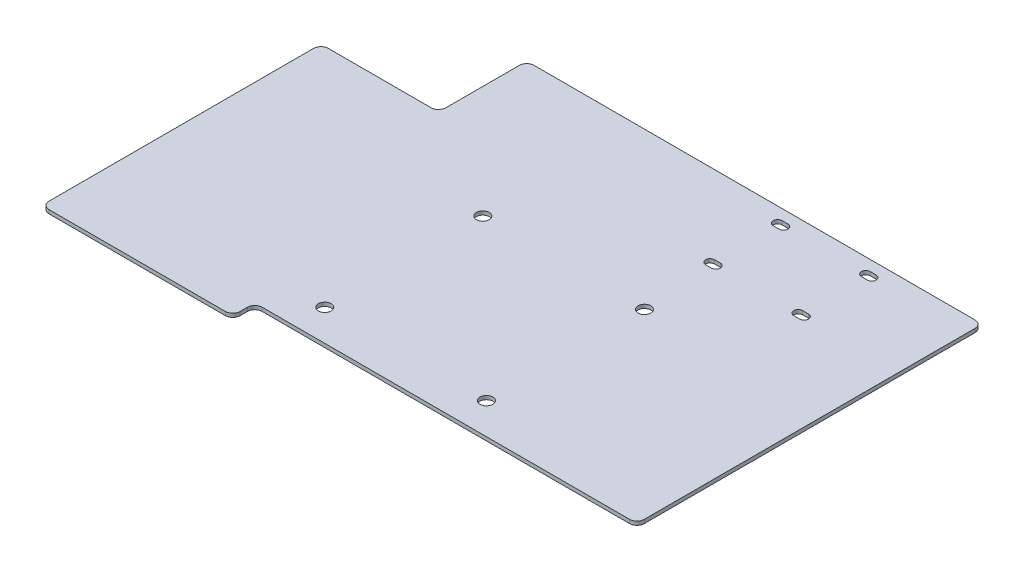
SolidWorks part; units mm, degrees
ref_plane "Front Plane" through (0, 0, 0) normal (0, 0, 1) x (1, 0, 0)
ref_plane "Top Plane" through (0, 0, 0) normal (0, 1, 0) x (1, 0, 0)
ref_plane "Right Plane" through (0, 0, 0) normal (1, 0, 0) x (0, 0, -1)
sketch "Sketch1" plane through (0, 0, 0) normal (0, 1, 0) x (1, 0, 0)
  line L1 (0, 0) -> (247.65, 0)
  line L2 (0, 0) -> (0, 120.65)
  line L3 (50.8, 158.75) -> (247.65, 158.75)
  line L4 (247.65, 0) -> (247.65, 158.75)
  line L15 (0, 120.65) -> (50.8, 120.65)
  line L16 (50.8, 158.75) -> (50.8, 120.65)
  line L21 (351.9786, 184.7613) -> (351.9786, -3.4747) construction
  point P1 (-19.9866, 3.5414)
  point P2 (0, 0)
  dimension "D1" = 158.75
  dimension "D2" = 351.9786
  dimension "D4" = 247.65
  dimension "D6" = 38.1
  dimension "D7" = 50.8
extrude "Boss-Extrude1" add sketch "Sketch1" along normal blind 1.6002 contours L1 L4 L3 L2 L15 L16 region at (128.9214, 0, -76.2514)
sketch "Sketch3" plane through (0, 1.6002, 0) normal (0, 1, 0) x (1, 0, 0)
  line L0 (82.55, 0) -> (82.55, 9.525)
  line L1 (0, 0) -> (247.65, 0) construction
  line L2 (82.55, 9.525) -> (247.65, 9.525)
  line L8 (247.65, 0) -> (247.65, 158.75) construction
  line L10 (247.65, 0) -> (82.55, 0)
  line L11 (0, 0) -> (0, 120.65) construction
  line L12 (247.65, 9.525) -> (247.65, 0)
  point P5 (247.65, 9.525)
  point P7 (247.65, 12.1552)
  dimension "D1" = 82.55
  dimension "D2" = 9.525
extrude "Cut-Extrude1" cut sketch "Sketch3" against normal through all
fillet "Fillet1" radius 3.175 8 edges at (82.55, 0.8001, 0) (0, 0.8001, -120.65) (50.8, 0.8001, -120.65) (50.8, 0.8001, -158.75) (247.65, 0.8001, -158.75) (247.65, 0.8001, -9.525) (82.55, 0.8001, -9.525) (0, 0.8001, 0)
sketch "Sketch4" plane through (0, 1.6002, 0) normal (0, 1, 0) x (1, 0, 0)
  line L0 (165.653, 152.32) -> (168.193, 152.32) construction
  line L1 (165.653, 154.225) -> (168.193, 154.225)
  line L2 (165.653, 150.415) -> (168.193, 150.415)
  line L5 (203.753, 152.32) -> (206.293, 152.32) construction
  line L6 (203.753, 154.225) -> (206.293, 154.225)
  line L7 (203.753, 150.415) -> (206.293, 150.415)
  line L8 (203.753, 123.11) -> (206.293, 123.11) construction
  line L9 (203.753, 125.015) -> (206.293, 125.015)
  line L10 (203.753, 121.205) -> (206.293, 121.205)
  line L11 (165.653, 123.11) -> (168.193, 123.11) construction
  line L12 (165.653, 125.015) -> (168.193, 125.015)
  line L13 (165.653, 121.205) -> (168.193, 121.205)
  line L15 (205.023, 123.11) -> (166.923, 123.11) construction
  line L16 (205.023, 123.11) -> (205.023, 152.32) construction
  line L17 (205.023, 152.32) -> (166.923, 152.32) construction
  line L18 (166.923, 123.11) -> (166.923, 152.32) construction
  line L19 (205.023, 123.11) -> (166.923, 152.32) construction
  line L20 (205.023, 152.32) -> (166.923, 123.11) construction
  line L21 (222.488, 125.015) -> (149.458, 125.015) construction
  line L22 (222.488, 125.015) -> (222.488, 150.415) construction
  line L23 (222.488, 150.415) -> (149.458, 150.415) construction
  line L24 (149.458, 125.015) -> (149.458, 150.415) construction
  line L25 (222.488, 125.015) -> (149.458, 150.415) construction
  line L26 (222.488, 150.415) -> (149.458, 125.015) construction
  arc A0 (165.653, 154.225) -> (165.653, 150.415) centre (165.653, 152.32) ccw
  arc A1 (168.193, 150.415) -> (168.193, 154.225) centre (168.193, 152.32) ccw
  arc A2 (203.753, 154.225) -> (203.753, 150.415) centre (203.753, 152.32) ccw
  arc A3 (206.293, 150.415) -> (206.293, 154.225) centre (206.293, 152.32) ccw
  arc A4 (203.753, 125.015) -> (203.753, 121.205) centre (203.753, 123.11) ccw
  arc A5 (206.293, 121.205) -> (206.293, 125.015) centre (206.293, 123.11) ccw
  arc A6 (165.653, 125.015) -> (165.653, 121.205) centre (165.653, 123.11) ccw
  arc A7 (168.193, 121.205) -> (168.193, 125.015) centre (168.193, 123.11) ccw
  point P2 (166.923, 152.32)
  point P8 (222.488, 125.015)
  point P9 (149.458, 150.415)
  point P10 (205.023, 154.7275)
  point P12 (185.973, 137.715)
  point P13 (205.023, 152.32)
  point P20 (205.023, 123.11)
  point P27 (166.923, 123.11)
  point P36 (185.973, 137.715)
  point P41 (166.923, 123.745)
  point P42 (165.653, 150.415)
  dimension "D2" = 6.35
  dimension "D1" = 3.81
  dimension "D5" = 38.1
  dimension "D3" = 2
  dimension "D4" = 2
extrude "Fuse Ziptie Mounts" cut sketch "Sketch4" against normal through all
sketch "Sketch5" plane through (0, 1.6002, 0) normal (0, 1, 0) x (1, 0, 0)
  circle A0 centre (99.298, 91.2876) radius 2.75
  circle A1 centre (99.298, 23.0124) radius 2.75
  circle A2 centre (169.148, 91.2876) radius 2.75
  circle A3 centre (169.148, 23.0124) radius 2.75
  dimension "D1" = 5.5
extrude "Contactor Mounting Holes" cut sketch "Sketch5" against normal through all
